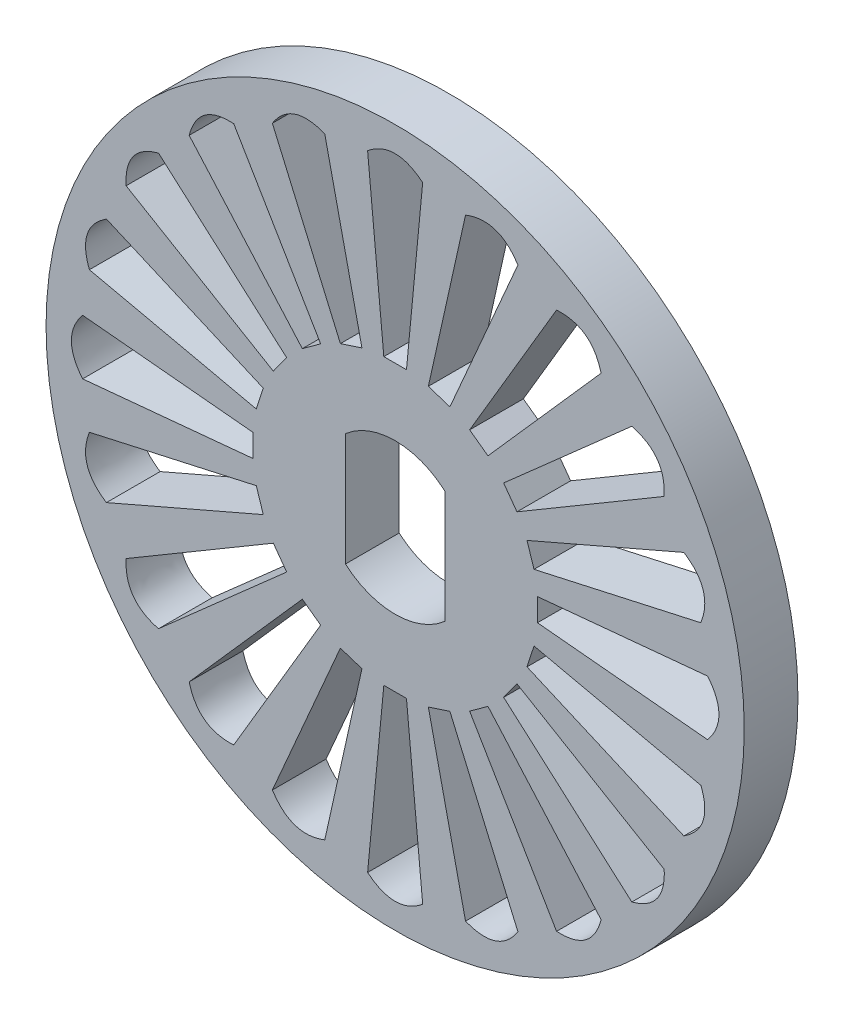
SolidWorks part; units mm, degrees
ref_plane "Front Plane" through (0, 0, 0) normal (0, 0, 1) x (1, 0, 0)
ref_plane "Top Plane" through (0, 0, 0) normal (0, 1, 0) x (1, 0, 0)
ref_plane "Right Plane" through (0, 0, 0) normal (1, 0, 0) x (0, 0, -1)
sketch "Sketch1" plane through (0, 0, 0) normal (0, 0, 1) x (1, 0, 0)
  line L0 (0, 29.3396) -> (0, -28.4316) construction
  line L1 (-34.5346, 0) -> (35.2675, 0) construction
  circle A0 centre (0, 0) radius 13
  dimension "D1" = 26
extrude "Boss-Extrude1" add sketch "Sketch1" along normal blind 2
sketch "Sketch2" plane through (0, 0, 2) normal (0, 0, 1) x (1, 0, 0)
  line L0 (0, 12.0457) -> (0, -12.3213) construction
  line L1 (-16.0712, 0) -> (16.7447, 0) construction
  line L2 (1.85, 2.1018) -> (1.85, -2.1018)
  line L3 (-1.85, 2.1018) -> (-1.85, -2.1018)
  arc A0 (-1.85, -2.1018) -> (1.85, -2.1018) centre (0, 0) ccw
  arc A1 (1.85, 2.1018) -> (-1.85, 2.1018) centre (0, 0) ccw
  dimension "D1" = 3.7
  dimension "D2" = 5.6
extrude "Cut-Extrude1" cut sketch "Sketch2" against normal blind 2
sketch "Sketch3" plane through (0, 0, 2) normal (0, 0, 1) x (1, 0, 0)
  line L0 (0, 13.934) -> (0, -12.3825) construction
  line L1 (-14.8773, 0) -> (14.2345, 0) construction
  line L2 (-0.4219, 5.3) -> (0.4219, 5.3)
  line L3 (0.4219, 5.3) -> (1.0258, 11.6382)
  line L4 (-0.4219, 5.3) -> (-1.0258, 11.6382)
  line L6 (2.039, 4.9102) -> (4.572, 10.7516)
  line L7 (1.2365, 5.171) -> (2.039, 4.9102)
  line L8 (1.2365, 5.171) -> (2.6209, 11.3856)
  line L9 (3.4566, 4.0398) -> (7.6706, 8.8126)
  line L10 (2.7739, 4.5358) -> (3.4566, 4.0398)
  line L11 (2.7739, 4.5358) -> (6.0109, 10.0184)
  line L12 (4.5358, 2.7739) -> (10.0184, 6.0109)
  line L13 (4.0398, 3.4566) -> (4.5358, 2.7739)
  line L14 (4.0398, 3.4566) -> (8.8126, 7.6706)
  line L15 (5.171, 1.2365) -> (11.3856, 2.6209)
  line L16 (4.9102, 2.039) -> (5.171, 1.2365)
  line L17 (4.9102, 2.039) -> (10.7516, 4.572)
  line L18 (5.3, -0.4219) -> (11.6382, -1.0258)
  line L19 (5.3, 0.4219) -> (5.3, -0.4219)
  line L20 (5.3, 0.4219) -> (11.6382, 1.0258)
  line L21 (4.9102, -2.039) -> (10.7516, -4.572)
  line L22 (5.171, -1.2365) -> (4.9102, -2.039)
  line L23 (5.171, -1.2365) -> (11.3856, -2.6209)
  line L24 (4.0398, -3.4566) -> (8.8126, -7.6706)
  line L25 (4.5358, -2.7739) -> (4.0398, -3.4566)
  line L26 (4.5358, -2.7739) -> (10.0184, -6.0109)
  line L27 (2.7739, -4.5358) -> (6.0109, -10.0184)
  line L28 (3.4566, -4.0398) -> (2.7739, -4.5358)
  line L29 (3.4566, -4.0398) -> (7.6706, -8.8126)
  line L30 (1.2365, -5.171) -> (2.6209, -11.3856)
  line L31 (2.039, -4.9102) -> (1.2365, -5.171)
  line L32 (2.039, -4.9102) -> (4.572, -10.7516)
  line L33 (-0.4219, -5.3) -> (-1.0258, -11.6382)
  line L34 (0.4219, -5.3) -> (-0.4219, -5.3)
  line L35 (0.4219, -5.3) -> (1.0258, -11.6382)
  line L36 (-2.039, -4.9102) -> (-4.572, -10.7516)
  line L37 (-1.2365, -5.171) -> (-2.039, -4.9102)
  line L38 (-1.2365, -5.171) -> (-2.6209, -11.3856)
  line L39 (-3.4566, -4.0398) -> (-7.6706, -8.8126)
  line L40 (-2.7739, -4.5358) -> (-3.4566, -4.0398)
  line L41 (-2.7739, -4.5358) -> (-6.0109, -10.0184)
  line L42 (-4.5358, -2.7739) -> (-10.0184, -6.0109)
  line L43 (-4.0398, -3.4566) -> (-4.5358, -2.7739)
  line L44 (-4.0398, -3.4566) -> (-8.8126, -7.6706)
  line L45 (-5.171, -1.2365) -> (-11.3856, -2.6209)
  line L46 (-4.9102, -2.039) -> (-5.171, -1.2365)
  line L47 (-4.9102, -2.039) -> (-10.7516, -4.572)
  line L48 (-5.3, 0.4219) -> (-11.6382, 1.0258)
  line L49 (-5.3, -0.4219) -> (-5.3, 0.4219)
  line L50 (-5.3, -0.4219) -> (-11.6382, -1.0258)
  line L51 (-4.9102, 2.039) -> (-10.7516, 4.572)
  line L52 (-5.171, 1.2365) -> (-4.9102, 2.039)
  line L53 (-5.171, 1.2365) -> (-11.3856, 2.6209)
  line L54 (-4.0398, 3.4566) -> (-8.8126, 7.6706)
  line L55 (-4.5358, 2.7739) -> (-4.0398, 3.4566)
  line L56 (-4.5358, 2.7739) -> (-10.0184, 6.0109)
  line L57 (-2.7739, 4.5358) -> (-6.0109, 10.0184)
  line L58 (-3.4566, 4.0398) -> (-2.7739, 4.5358)
  line L59 (-3.4566, 4.0398) -> (-7.6706, 8.8126)
  line L60 (-1.2365, 5.171) -> (-2.6209, 11.3856)
  line L61 (-2.039, 4.9102) -> (-1.2365, 5.171)
  line L62 (-2.039, 4.9102) -> (-4.572, 10.7516)
  arc A2 (1.85, 2.1018) -> (-1.85, 2.1018) centre (0, 0) ccw construction
  spline S0 degree 2 poles (-1.0258, 11.6382) (0, 12.4761) (1.0258, 11.6382) knots 0 0 0 1 1 1
  spline S1 degree 2 poles (2.6209, 11.3856) (3.8553, 11.8655) (4.572, 10.7516) knots 0 0 0 1 1 1
  spline S2 degree 2 poles (6.0109, 10.0184) (7.3333, 10.0934) (7.6706, 8.8126) knots 0 0 0 1 1 1
  spline S3 degree 2 poles (8.8126, 7.6706) (10.0934, 7.3333) (10.0184, 6.0109) knots 0 0 0 1 1 1
  spline S4 degree 2 poles (10.7516, 4.572) (11.8655, 3.8553) (11.3856, 2.6209) knots 0 0 0 1 1 1
  spline S5 degree 2 poles (11.6382, 1.0258) (12.4761, 0) (11.6382, -1.0258) knots 0 0 0 1 1 1
  spline S6 degree 2 poles (11.3856, -2.6209) (11.8655, -3.8553) (10.7516, -4.572) knots 0 0 0 1 1 1
  spline S7 degree 2 poles (10.0184, -6.0109) (10.0934, -7.3333) (8.8126, -7.6706) knots 0 0 0 1 1 1
  spline S8 degree 2 poles (7.6706, -8.8126) (7.3333, -10.0934) (6.0109, -10.0184) knots 0 0 0 1 1 1
  spline S9 degree 2 poles (4.572, -10.7516) (3.8553, -11.8655) (2.6209, -11.3856) knots 0 0 0 1 1 1
  spline S10 degree 2 poles (1.0258, -11.6382) (0, -12.4761) (-1.0258, -11.6382) knots 0 0 0 1 1 1
  spline S11 degree 2 poles (-2.6209, -11.3856) (-3.8553, -11.8655) (-4.572, -10.7516) knots 0 0 0 1 1 1
  spline S12 degree 2 poles (-6.0109, -10.0184) (-7.3333, -10.0934) (-7.6706, -8.8126) knots 0 0 0 1 1 1
  spline S13 degree 2 poles (-8.8126, -7.6706) (-10.0934, -7.3333) (-10.0184, -6.0109) knots 0 0 0 1 1 1
  spline S14 degree 2 poles (-10.7516, -4.572) (-11.8655, -3.8553) (-11.3856, -2.6209) knots 0 0 0 1 1 1
  spline S15 degree 2 poles (-11.6382, -1.0258) (-12.4761, 0) (-11.6382, 1.0258) knots 0 0 0 1 1 1
  spline S16 degree 2 poles (-11.3856, 2.6209) (-11.8655, 3.8553) (-10.7516, 4.572) knots 0 0 0 1 1 1
  spline S17 degree 2 poles (-10.0184, 6.0109) (-10.0934, 7.3333) (-8.8126, 7.6706) knots 0 0 0 1 1 1
  spline S18 degree 2 poles (-7.6706, 8.8126) (-7.3333, 10.0934) (-6.0109, 10.0184) knots 0 0 0 1 1 1
  spline S19 degree 2 poles (-4.572, 10.7516) (-3.8553, 11.8655) (-2.6209, 11.3856) knots 0 0 0 1 1 1
  point P91 (0, 0)
  point P121 (0, 0)
  point P122 (0, 0)
  point P137 (0, 0)
  point P152 (0, 0)
  point P180 (0, 0)
  point P181 (0, 0)
  dimension "D2" = 2.5
  dimension "D1" = 20
extrude "Cut-Extrude2" cut sketch "Sketch3" against normal blind 2
